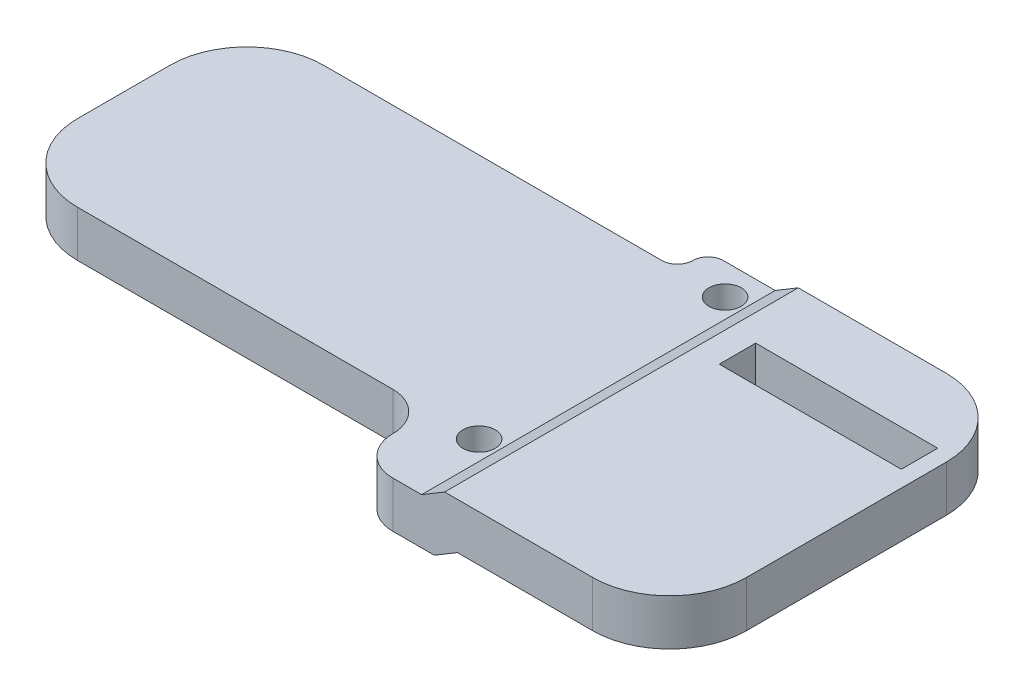
SolidWorks part; units mm, degrees
material "ABS"
ref_plane "Front" through (0, 0, 0) normal (0, 0, 1) x (1, 0, 0)
ref_plane "Top" through (0, 0, 0) normal (0, 1, 0) x (1, 0, 0)
ref_plane "Right" through (0, 0, 0) normal (1, 0, 0) x (0, 0, -1)
sketch "Sketch1" plane through (0, 0, 0) normal (0, 1, 0) x (1, 0, 0)
  line L0 (4.5, 8) -> (27.1, 8) construction
  line L6 (0, 16) -> (28, 16)
  line L7 (0, 16) -> (0, 0)
  line L8 (0, 0) -> (28, 0)
  line L9 (28, 16) -> (28, 0)
  dimension "D1" = 16
  dimension "D2" = 28
extrude "Boss-Extrude1" add sketch "Sketch1" along normal blind 3 contours L9 L6 L7 L8 | L9 | L9 region at (14, 0, -8)
sketch "Esquisse1" plane through (0, 0, 0) normal (0, 0, 1) x (1, 0, 0)
  line L0 (32.369, 3) -> (33.869, 3.9)
  line L1 (33.869, 3.9) -> (48.5, 3.9)
  line L2 (48.5, 3.9) -> (48.5, 0.9)
  line L3 (48.5, 0.9) -> (34.7, 0.9)
  line L4 (34.7, 0.9) -> (33.2, 0)
  line L5 (28, 0) -> (33.2, 0)
  line L6 (0, 0) -> (28, 0) construction
  line L11 (28, 3) -> (32.369, 3)
  line L12 (28, 3) -> (28, 0)
  dimension "D1" = 3
  dimension "D2" = 15.3
  dimension "D3" = 1.5
  dimension "D4" = 0.9
  dimension "D5" = 3
  dimension "D6" = 5.2
extrude "Boss.-Extru.1" add sketch "Esquisse1" against normal blind 18 and the other way blind 5 contours L4 L5 L12 L11 L0 L1 L2 L3
sketch "Esquisse8" plane through (0, 3.9, 0) normal (0, 1, 0) x (1, 0, 0)
  line L0 (33.869, 18) -> (48.5, 18) construction
  line L1 (35.6, 13.5) -> (47.44, 13.5)
  line L2 (35.6, 13.5) -> (35.6, 11.13)
  line L3 (35.6, 11.13) -> (47.44, 11.13)
  line L4 (47.44, 13.5) -> (47.44, 11.13)
  line L6 (28, 16) -> (28, 18) construction
  dimension "D1" = 4.5
  dimension "D2" = 2.37
  dimension "D3" = 11.84
  dimension "D4" = 7.6
extrude "Enlèv. mat.-Extru.4" cut sketch "Esquisse8" against normal blind 10
sketch "Esquisse9" plane through (0, 0, 0) normal (0, -1, 0) x (1, 0, 0)
  line L0 (0, -16) -> (0, 0) construction
  line L1 (4.5, -2.08) -> (27.1, -2.08)
  line L2 (4.5, -2.08) -> (4.5, -13.92)
  line L3 (4.5, -13.92) -> (27.1, -13.92)
  line L4 (27.1, -2.08) -> (27.1, -13.92)
  line L5 (27.1, -8) -> (4.5, -8) construction
  line L6 (0, -16) -> (28, -16) construction
  line L7 (0, 0) -> (28, 0) construction
  dimension "D1" = 11.84
  dimension "D2" = 22.6
  dimension "D3" = 4.5
extrude "Enlèv. mat.-Extru.5" cut sketch "Esquisse9" against normal blind 1
sketch "Esquisse10" plane through (0, 0, 0) normal (0, -1, 0) x (1, 0, 0)
  line L0 (27.1, -13.92) -> (27.1, -2.08) construction
  line L2 (31.11, -16) -> (31.11, 0) construction
  line L3 (31.11, -8) -> (34.0188, -8) construction
  line L4 (0, 0) -> (28, 0) construction
  line L5 (0, -16) -> (28, -16) construction
  circle A2 centre (31.11, 0) radius 1.05
  circle A3 centre (31.11, -16) radius 1.05
  dimension "D1" = 2.1
  dimension "D2" = 2.1
  dimension "D3" = 4.01
  dimension "D4" = 16
extrude "Enlèv. mat.-Extru.6" cut sketch "Esquisse10" against normal through all
fillet "Congé3" radius 1 2 edges at (28, 1.5, -18)
fillet "Congé4" radius 5 4 edges at (48.5, 2.4, -18) (48.5, 2.4, 5) (0, 1.5, 0) (0, 1.5, -16)
fillet "Congé5" radius 2.5 2 edges at (28, 1.5, 5)
